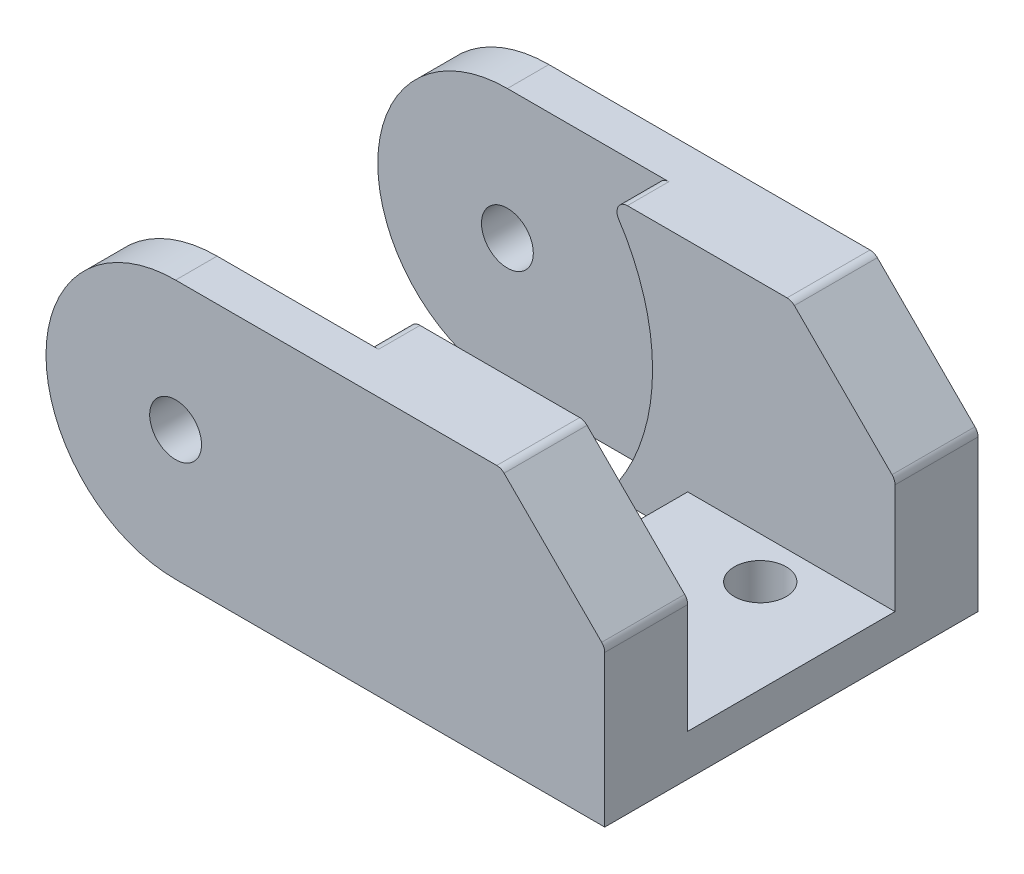
SolidWorks part; units mm, degrees
ref_plane "Front Plane" through (0, 0, 0) normal (0, 0, 1) x (1, 0, 0)
ref_plane "Top Plane" through (0, 0, 0) normal (0, 1, 0) x (1, 0, 0)
ref_plane "Right Plane" through (0, 0, 0) normal (1, 0, 0) x (0, 0, -1)
sketch "Sketch1" plane through (0, 0, 0) normal (0, 0, 1) x (1, 0, 0)
  line L0 (0, 12.5) -> (26.3875, 12.5)
  line L1 (20, 12.5) -> (20, -12.5) construction
  line L2 (26.3875, -12.5) -> (0, -12.5)
  line L3 (13.6125, -12.5) -> (40, -12.5)
  line L4 (40, 12.5) -> (13.6125, 12.5)
  circle A0 centre (0, 0) radius 12.5
  arc A1 (26.3875, -12.5) -> (26.3875, 12.5) centre (42, 0) cw
  arc A2 (13.6125, -12.5) -> (13.6125, 12.5) centre (-2, 0) ccw
  circle A3 centre (40, 0) radius 12.5
  dimension "D1" = 25
  dimension "D3" = 42
  dimension "D4" = 20
  dimension "D2" = 20
extrude "Boss-Extrude1" add sketch "Sketch1" along normal blind 4 contours A0 | L4 L1 L2 A1 | L2 A2 L0 A0 | L1 L0 A2 L3 region at (12.761, 0, 0) region at (0, 0, 0) region at (18.0615, 0, 0) region at (21.9385, 0, 0)
sketch "Sketch8" plane through (0, 0, 0) normal (0, 0, -1) x (-1, 0, 0)
  line L0 (-26.3875, 12.5) -> (-41.3875, 12.5)
  line L2 (-26.3875, -12.5) -> (-41.3875, -12.5)
  line L3 (-41.3875, -12.5) -> (-41.3875, 12.5)
  arc A0 (-26.3875, -12.5) -> (-26.3875, 12.5) centre (-42, 0) ccw construction
  arc A1 (-26.3875, -12.5) -> (-26.3875, 12.5) centre (-42, 0) ccw
  dimension "D1" = 15
extrude "Boss-Extrude7" add sketch "Sketch8" against normal blind 4
ref_plane "Plane2" through (0, 0, 18) normal (0, 0, 1) x (1, 0, 0)
mirror "Mirror3" about plane through (0, 0, 18) normal (0, 0, 1) of bodies 109
sketch "Sketch9" plane through (0, -12.5, 0) normal (0, -1, 0) x (1, 0, 0)
  line L0 (41.3875, 0) -> (0, 0) construction
  line L1 (41.3875, 36) -> (21.3875, 36)
  line L2 (41.3875, 36) -> (41.3875, 0)
  line L3 (41.3875, 0) -> (21.3875, 0)
  line L4 (21.3875, 36) -> (21.3875, 0)
  dimension "D1" = 20
extrude "Boss-Extrude8" add sketch "Sketch9" against normal blind 4
extrude "Boss-Extrude9" add sketch "Sketch1<4>" along normal blind 8 contours L1 L0 A2 L3 | L4 L1 L2 A1 | L3 A3 L4 A1 region at (18.0615, 0, 0) region at (21.9385, 0, 0) region at (27.239, 0, 0)
sketch "Sketch1<4>" plane through (0, 0, 0) normal (0, 0, 1) x (1, 0, 0) same geometry as "Sketch1"
sketch "Sketch10" plane through (0, 0, 4) normal (0, 0, 1) x (1, 0, 0)
  line L3 (41.3875, 12.5) -> (40, 12.5)
  line L4 (30.8348, -8.5) -> (41.3875, -8.5)
  line L5 (41.3875, -8.5) -> (41.3875, 12.5)
  line L6 (41.3875, 12.5) -> (40, 12.5)
  line L7 (30.8348, -8.5) -> (41.3875, -8.5)
  line L8 (41.3875, -8.5) -> (41.3875, 12.5)
  arc A1 (40, 12.5) -> (30.8348, -8.5) centre (40, 0) ccw
  arc A2 (40, 12.5) -> (30.8348, -8.5) centre (40, 0) ccw
  dimension "D1" = 0
extrude "Boss-Extrude10" add sketch "Sketch10" along normal blind 4
mirror "Mirror4" about plane through (0, 0, 18) normal (0, 0, 1) of "Boss-Extrude9", "Boss-Extrude10"
fillet "Fillet4" radius 1 4 edges at (13.6125, -12.5, 30) (13.6125, 12.5, 30) (13.6125, -12.5, 6) (13.6125, 12.5, 6)
sketch "Sketch11" plane through (0, 0, 36) normal (0, 0, 1) x (1, 0, 0)
  circle A0 centre (0, 0) radius 2.5
  dimension "D1" = 5
extrude "Cut-Extrude2" cut sketch "Sketch11" against normal through all
chamfer "Chamfer1" distance 10 angle 45 2 edges at (41.3875, 12.5, 32) (41.3875, 12.5, 4)
sketch "Sketch12" plane through (0, -8.5, 0) normal (0, 1, 0) x (1, 0, 0)
  line L0 (41.3875, -8) -> (41.3875, -28) construction
  line L2 (41.3875, -8) -> (31.3875, -8) construction
  line L3 (41.3875, -18) -> (45.3648, -18) construction
  circle A0 centre (32.3875, -12) radius 2.5
  circle A1 centre (32.3875, -24) radius 2.5
  dimension "D1" = 5
  dimension "D2" = 9
  dimension "D3" = 4
extrude "Cut-Extrude3" cut sketch "Sketch12" against normal blind 4
fillet "Fillet5" radius 1 4 edges at (41.3875, 2.5, 32) (41.3875, 2.5, 4) (31.3875, 12.5, 4) (31.3875, 12.5, 32)
sketch "Sketch13" plane through (0, -12.5, 0) normal (0, -1, 0) x (1, 0, 0)
  line L0 (41.3875, 36) -> (41.3875, 0) construction
  point P0 (41.3875, 18)
scale "Scale1" bodies to scale 116 scale about origin uniform scaling yes scale factor 0.5
